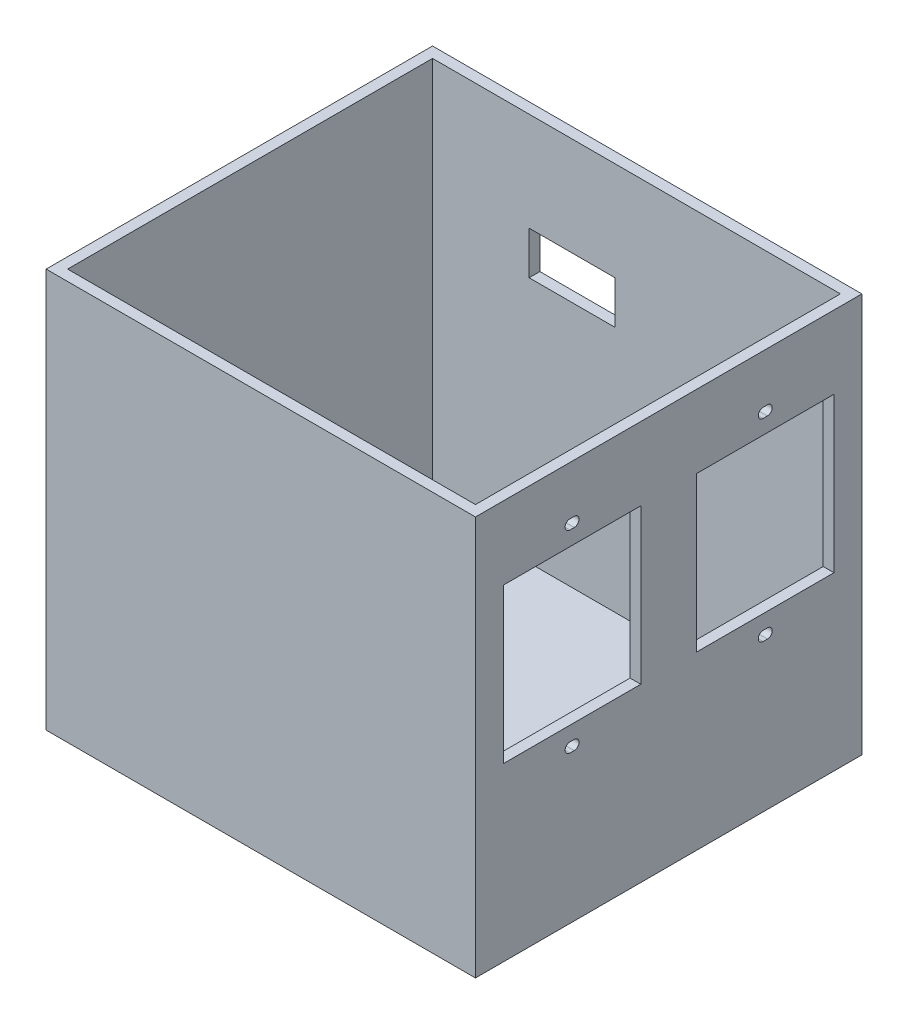
SolidWorks part; units mm, degrees
ref_plane "Front Plane" through (0, 0, 0) normal (0, 0, 1) x (1, 0, 0)
ref_plane "Top Plane" through (0, 0, 0) normal (0, 1, 0) x (1, 0, 0)
ref_plane "Right Plane" through (0, 0, 0) normal (1, 0, 0) x (0, 0, -1)
sketch "Sketch1" plane through (0, 0, 0) normal (0, 1, 0) x (1, 0, 0)
  line L0 (47.5, 42.5) -> (-47.5, 42.5)
  line L1 (50, 45) -> (-50, 45)
  line L2 (50, 45) -> (50, -45)
  line L3 (50, -45) -> (-50, -45)
  line L4 (-50, 45) -> (-50, -45)
  line L5 (50, 45) -> (-50, -45) construction
  line L6 (50, -45) -> (-50, 45) construction
  line L7 (-47.5, 42.5) -> (-47.5, -42.5)
  line L8 (47.5, -42.5) -> (-47.5, -42.5)
  line L9 (47.5, 42.5) -> (47.5, -42.5)
  point P0 (0, 0)
  dimension "D1" = 90
  dimension "D2" = 100
  dimension "D3" = 2.5
extrude "Boss-Extrude1" add sketch "Sketch1" along normal blind 2.5 contours L9 L0 L7 L8 | L1 L4 L3 L2 L0 L9 L8 L7 region at (0, 0, 0) region at (48.6546, 0, 0)
extrude "Boss-Extrude2" add sketch "Sketch1<3>" along normal blind 93
sketch "Sketch1<3>" plane through (0, 0, 0) normal (0, 1, 0) x (1, 0, 0) same geometry as "Sketch1"
sketch "Sketch2" plane through (50, 0, 0) normal (1, 0, 0) x (0, 0, -1)
  line L0 (0, 93) -> (0, 0) construction
  line L1 (-45, 93) -> (45, 93) construction
  line L2 (-23, 80.5) -> (-22, 80.5) construction
  line L3 (-6.5, 40) -> (-38.5, 40)
  line L4 (-6.5, 40) -> (-6.5, 76)
  line L5 (-6.5, 76) -> (-38.5, 76)
  line L6 (-38.5, 40) -> (-38.5, 76)
  line L7 (-6.5, 40) -> (-38.5, 76) construction
  line L8 (-6.5, 76) -> (-38.5, 40) construction
  line L11 (-23, 81.625) -> (-22, 81.625)
  line L12 (-23, 79.375) -> (-22, 79.375)
  line L13 (-48.2126, 58) -> (-0.6327, 58) construction
  line L14 (-23, 35.5) -> (-22, 35.5) construction
  line L15 (-23, 34.375) -> (-22, 34.375)
  line L16 (-23, 36.625) -> (-22, 36.625)
  line L17 (48.2126, 58) -> (0.6327, 58) construction
  line L18 (6.5, 76) -> (38.5, 40) construction
  line L19 (6.5, 40) -> (38.5, 76) construction
  line L20 (38.5, 40) -> (38.5, 76)
  line L21 (6.5, 76) -> (38.5, 76)
  line L22 (6.5, 40) -> (6.5, 76)
  line L23 (6.5, 40) -> (38.5, 40)
  line L24 (23, 35.5) -> (22, 35.5) construction
  line L25 (23, 34.375) -> (22, 34.375)
  line L26 (23, 36.625) -> (22, 36.625)
  line L27 (23, 80.5) -> (22, 80.5) construction
  line L28 (23, 81.625) -> (22, 81.625)
  line L29 (23, 79.375) -> (22, 79.375)
  arc A2 (-23, 81.625) -> (-23, 79.375) centre (-23, 80.5) ccw
  arc A3 (-22, 79.375) -> (-22, 81.625) centre (-22, 80.5) ccw
  arc A4 (-23, 34.375) -> (-23, 36.625) centre (-23, 35.5) cw
  arc A5 (-22, 36.625) -> (-22, 34.375) centre (-22, 35.5) cw
  arc A6 (23, 34.375) -> (23, 36.625) centre (23, 35.5) ccw
  arc A7 (22, 36.625) -> (22, 34.375) centre (22, 35.5) ccw
  arc A8 (23, 81.625) -> (23, 79.375) centre (23, 80.5) cw
  arc A9 (22, 79.375) -> (22, 81.625) centre (22, 80.5) cw
  point P5 (-22.5, 58)
  point P12 (-22.5, 80.5)
  point P17 (-22.5, 81.625)
  point P22 (-22.5, 35.5)
  point P35 (22.5, 35.5)
  point P42 (22.5, 80.5)
  point P47 (22.5, 58)
  dimension "D1" = 32
  dimension "D2" = 36
  dimension "D3" = 22.5
  dimension "D4" = 35
  dimension "D5" = 16
  dimension "D6" = 2.25
  dimension "D7" = 45
  dimension "D8" = 1
extrude "Cut-Extrude1" cut sketch "Sketch2" against normal blind 5
sketch "Sketch3" plane through (0, 0, -45) normal (0, 0, -1) x (-1, 0, 0)
  line L0 (-50, 0) -> (50, 0) construction
  line L1 (5, 70) -> (25, 70)
  line L2 (5, 70) -> (5, 60)
  line L3 (5, 60) -> (25, 60)
  line L4 (25, 70) -> (25, 60)
  line L5 (5, 70) -> (25, 60) construction
  line L6 (5, 60) -> (25, 70) construction
  line L7 (-50, 93) -> (-50, 0) construction
  point P0 (15, 65)
  dimension "D1" = 20
  dimension "D2" = 10
  dimension "D3" = 65
  dimension "D4" = 65
extrude "Cut-Extrude2" cut sketch "Sketch3" against normal blind 5
